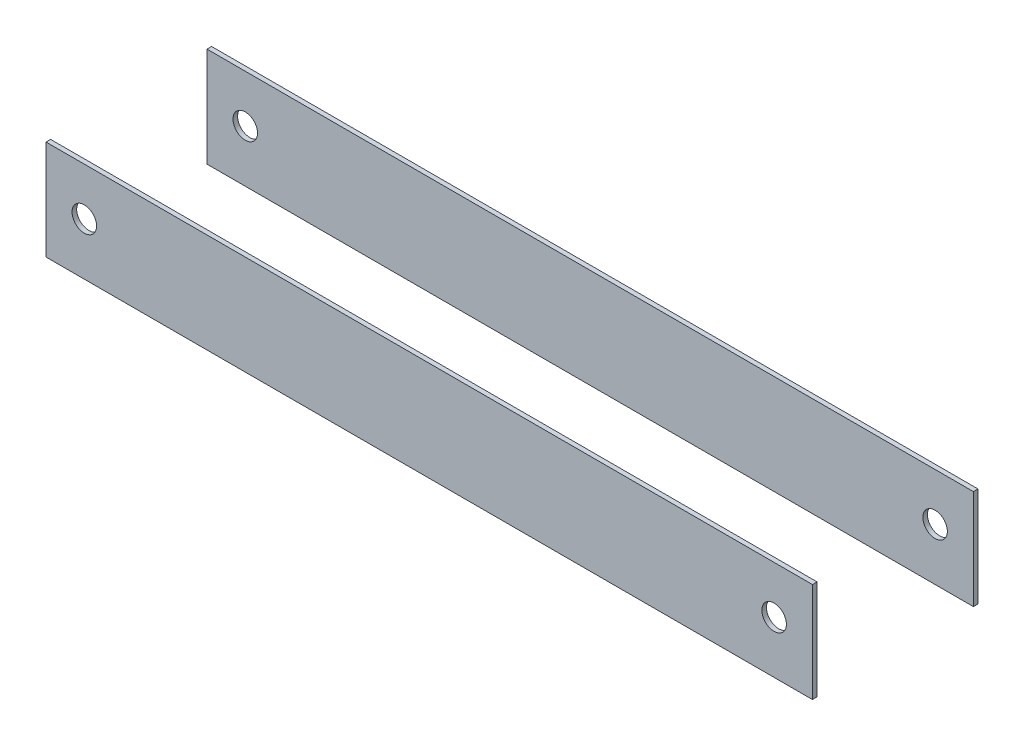
SolidWorks part; units mm, degrees
ref_plane "Front Plane" through (0, 0, 0) normal (0, 0, 1) x (1, 0, 0)
ref_plane "Top Plane" through (0, 0, 0) normal (0, 1, 0) x (1, 0, 0)
ref_plane "Right Plane" through (0, 0, 0) normal (1, 0, 0) x (0, 0, -1)
sketch "Sketch1" plane through (0, 0, 0) normal (0, 1, 0) x (1, 0, 0)
  line L1 (-233.8195, 144.485) -> (266.1805, 144.485)
  line L2 (-233.8195, 144.485) -> (-233.8195, 36.485)
  line L3 (-233.8195, 36.485) -> (266.1805, 36.485)
  line L4 (266.1805, 144.485) -> (266.1805, 36.485)
  line L5 (-233.8195, 141.485) -> (266.1805, 141.485)
  line L6 (-233.8195, 141.485) -> (-233.8195, 39.485)
  line L7 (-233.8195, 39.485) -> (266.1805, 39.485)
  line L8 (266.1805, 141.485) -> (266.1805, 39.485)
  dimension "D1" = 500
  dimension "D2" = 108
  dimension "D3" = 3
  dimension "D4" = 3
extrude "Boss-Extrude1" add sketch "Sketch1" along normal blind 65 contours L3 L4 L1 L2
sketch "Sketch3" plane through (0, 0, 0) normal (0, -1, 0) x (1, 0, 0)
  line L0 (-233.8195, -144.485) -> (-233.8195, -36.485) construction
  line L1 (-233.8195, -39.485) -> (266.1805, -39.485)
  line L2 (-233.8195, -39.485) -> (-233.8195, -141.485)
  line L3 (-233.8195, -141.485) -> (266.1805, -141.485)
  line L4 (266.1805, -39.485) -> (266.1805, -141.485)
  line L5 (266.1805, -144.485) -> (266.1805, -36.485) construction
  line L6 (-233.8195, -36.485) -> (266.1805, -36.485) construction
  line L7 (-233.8195, -144.485) -> (266.1805, -144.485) construction
  dimension "D1" = 3
  dimension "D2" = 3
extrude "Cut-Extrude1" cut sketch "Sketch3" against normal blind 158
sketch "Sketch4" plane through (0, 0, -36.485) normal (0, 0, 1) x (1, 0, 0)
  line L0 (-233.8195, 65) -> (266.1805, 65) construction
  line L1 (-233.8195, 65) -> (-233.8195, 0) construction
  line L2 (266.1805, 65) -> (266.1805, 0) construction
  circle A0 centre (-208.8195, 34) radius 8
  circle A1 centre (241.1805, 34) radius 8
  dimension "D1" = 16
  dimension "D2" = 31
  dimension "D3" = 25
  dimension "D4" = 25
  dimension "D5" = 16
  dimension "D6" = 31
extrude "Cut-Extrude2" cut sketch "Sketch4" against normal blind 158
